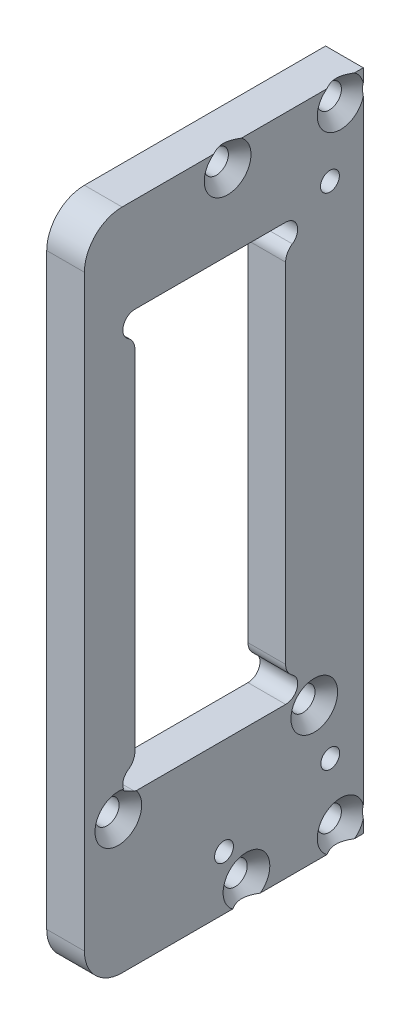
SolidWorks part; units mm, degrees
ref_plane "Front Plane" through (0, 0, 0) normal (1, 0, 0) x (0, 1, 0)
ref_plane "Top Plane" through (0, 0, 0) normal (0, 0, 1) x (0, 1, 0)
ref_plane "Right Plane" through (0, 0, 0) normal (0, 1, 0) x (-1, 0, 0)
sketch "Sketch1" plane through (0, 0, 0) normal (1, 0, 0) x (0, 1, 0)
  line L0 (0, 0) -> (0, -26.7331) construction
  line L1 (-44, 18.5) -> (44, 18.5)
  line L2 (-44, 18.5) -> (-44, -18.5)
  line L3 (-44, -18.5) -> (44, -18.5)
  line L4 (44, 18.5) -> (44, -18.5)
  line L5 (-44, 18.5) -> (44, -18.5) construction
  line L6 (-44, -18.5) -> (44, 18.5) construction
  line L7 (-24, -8.2) -> (-24, 11.8)
  line L8 (-19.4067, 11.8) -> (26.8067, 11.8)
  line L9 (31.4, 11.8) -> (31.4, -8.2)
  line L10 (26.8067, -8.2) -> (-19.4067, -8.2)
  line L11 (-32.5, 12.8) -> (-32.5, -9.2) construction
  line L12 (-32.5, 1.8) -> (31.4, 1.8) construction
  line L13 (-24, 1.8) -> (-30, 1.8) construction
  circle A1 centre (-41.5, -15.5) radius 1.6
  circle A2 centre (-41.5, -3) radius 1.6
  circle A4 centre (41.5, -15.5) radius 1.6
  circle A5 centre (-26, 14) radius 1.6
  circle A6 centre (-26, -12) radius 1.6
  arc A10 (-21.0696, 12.6889) -> (-24, 11.8) centre (-22.4, 11.8) ccw
  arc A11 (-21.0696, 12.6889) -> (-19.4067, 11.8) centre (-19.4067, 13.8) ccw
  arc A12 (28.4696, 12.6889) -> (26.8067, 11.8) centre (26.8067, 13.8) cw
  arc A13 (28.4696, 12.6889) -> (31.4, 11.8) centre (29.8, 11.8) cw
  arc A14 (28.4696, -9.0889) -> (31.4, -8.2) centre (29.8, -8.2) ccw
  arc A15 (28.4696, -9.0889) -> (26.8067, -8.2) centre (26.8067, -10.2) ccw
  arc A16 (-21.0696, -9.0889) -> (-19.4067, -8.2) centre (-19.4067, -10.2) cw
  arc A17 (-21.0696, -9.0889) -> (-24, -8.2) centre (-22.4, -8.2) cw
  circle A18 centre (41.5, -0.5) radius 1.6
  point P0 (0, 0)
  dimension "D3" = 3.2
  dimension "D4" = 3
  dimension "D5" = 3.2
  dimension "D10" = 3.2
  dimension "D11" = 3.2
  dimension "D8" = 2.5
  dimension "D16" = 20
  dimension "D14" = 18
  dimension "D13" = 26
  dimension "D17" = 15
  dimension "D1" = 37
  dimension "D2" = 88
  dimension "D6" = 12.5
  dimension "D7" = 2.5
  dimension "D9" = 15.5
  dimension "D12" = 4.5
  dimension "D15" = 6.7
  dimension "D18" = 0
extrude "Boss-Extrude1" add sketch "Sketch1" along normal blind 5
fillet "Fillet1" radius 5 2 edges at (2.5, 44, 18.5) (2.5, -44, 18.5)
chamfer "Chamfer2" distance 1.5 angle 45 6 edges at (5, -26, 12.4) (5, -26, -13.6) (5, -41.5, -17.1) (5, -41.5, -4.6) (5, 41.5, -13.9) (5, 41.5, -2.1)
sketch "Sketch2" plane through (5, 0, 0) normal (1, 0, 0) x (0, 1, 0)
  circle A0 centre (-36.8266, -0.0231) radius 1.25
  circle A1 centre (-33.1674, -14.1207) radius 1.25
  circle A2 centre (33.1826, -14.0775) radius 1.25
extrude "Cut-Extrude1" cut sketch "Sketch2" against normal blind 10
